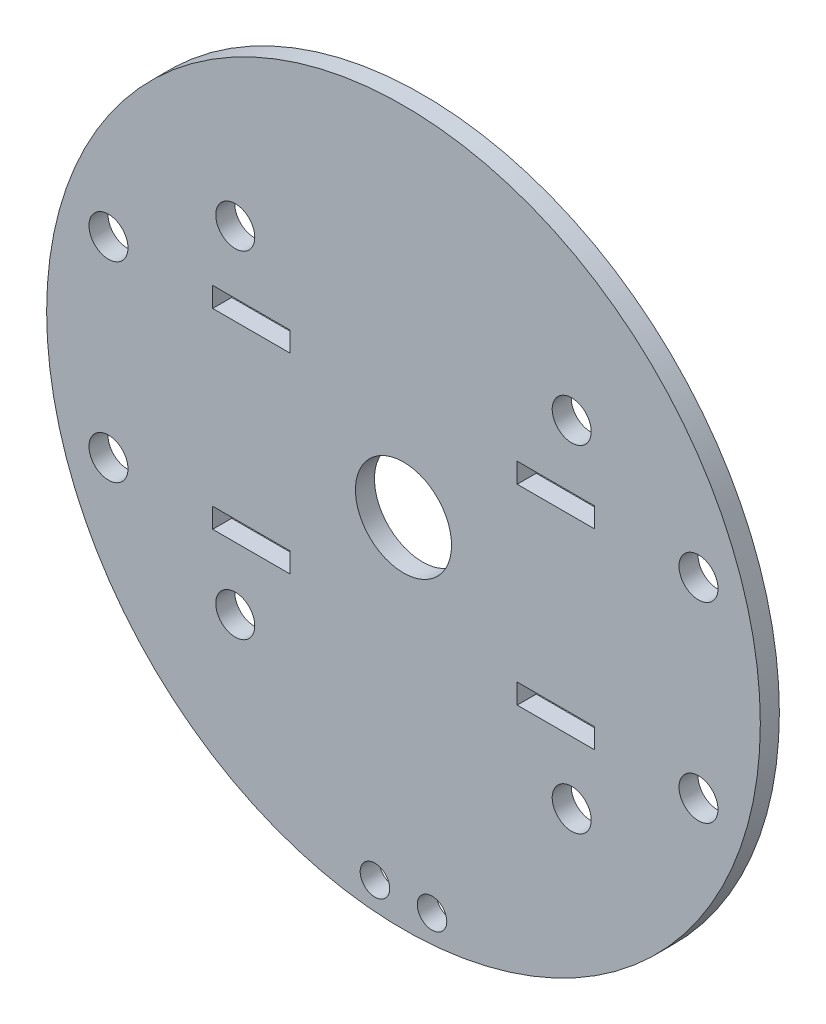
SolidWorks part; units mm, degrees
ref_plane "前视基准面" through (0, 0, 0) normal (0, 0, 1) x (1, 0, 0)
ref_plane "上视基准面" through (0, 0, 0) normal (0, 1, 0) x (1, 0, 0)
ref_plane "右视基准面" through (0, 0, 0) normal (1, 0, 0) x (0, 0, -1)
sketch "草图1" plane through (0, 0, 0) normal (0, 0, 1) x (1, 0, 0)
  line L0 (0, 0) -> (0, -37.5) construction
  line L1 (0, 0) -> (-28.479, -28.479) construction
  line L2 (3, -40.5) -> (-3, -40.5) construction
  line L3 (3, -40.5) -> (3, -34.5) construction
  line L4 (3, -34.5) -> (-3, -34.5) construction
  line L5 (-3, -40.5) -> (-3, -34.5) construction
  line L6 (3, -40.5) -> (-3, -34.5) construction
  line L7 (3, -34.5) -> (-3, -40.5) construction
  line L8 (20.05, -11.1) -> (20.05, -9)
  line L9 (11.95, -9) -> (20.05, -9)
  line L10 (11.95, -11.1) -> (11.95, -9)
  line L11 (11.95, -11.1) -> (20.05, -11.1)
  line L12 (0, 0) -> (37.5, 0) construction
  line L13 (11.95, 11.1) -> (11.95, 9)
  line L14 (20.05, 11.1) -> (20.05, 9)
  line L15 (11.95, 9) -> (20.05, 9)
  line L16 (11.95, 11.1) -> (20.05, 11.1)
  line L17 (-20.05, 11.1) -> (-20.05, 9)
  line L18 (-11.95, 11.1) -> (-11.95, 9)
  line L19 (-11.95, 9) -> (-20.05, 9)
  line L20 (-11.95, 11.1) -> (-20.05, 11.1)
  line L21 (-11.95, -11.1) -> (-11.95, -9)
  line L22 (-20.05, -11.1) -> (-20.05, -9)
  line L23 (-11.95, -9) -> (-20.05, -9)
  line L24 (-11.95, -11.1) -> (-20.05, -11.1)
  line L25 (-11.95, -9) -> (-20.05, -11.1) construction
  line L26 (-16, -10.05) -> (-31, -10.05) construction
  circle A0 centre (0, 0) radius 37.5
  circle A1 centre (0, 0) radius 5.05
  circle A2 centre (-3, -34.5) radius 1.55
  circle A3 centre (3, -34.5) radius 1.55
  circle A4 centre (0, 0) radius 25 construction
  circle A5 centre (-17.6777, -17.6777) radius 2.05
  circle A6 centre (-17.6777, 17.6777) radius 2.05
  circle A7 centre (17.6777, 17.6777) radius 2.05
  circle A8 centre (17.6777, -17.6777) radius 2.05
  circle A10 centre (-31, -10.05) radius 2.05
  circle A11 centre (-31, 10.05) radius 2.05
  circle A12 centre (31, 10.05) radius 2.05
  circle A13 centre (31, -10.05) radius 2.05
  dimension "D1" = 75
  dimension "D2" = 10.1
  dimension "D5" = 50
  dimension "D7" = 4
  dimension "D8" = 18
  dimension "D3" = 6
  dimension "D4" = 6
  dimension "D6" = 45
extrude "凸台-拉伸1" add sketch "草图1" along normal blind 2
